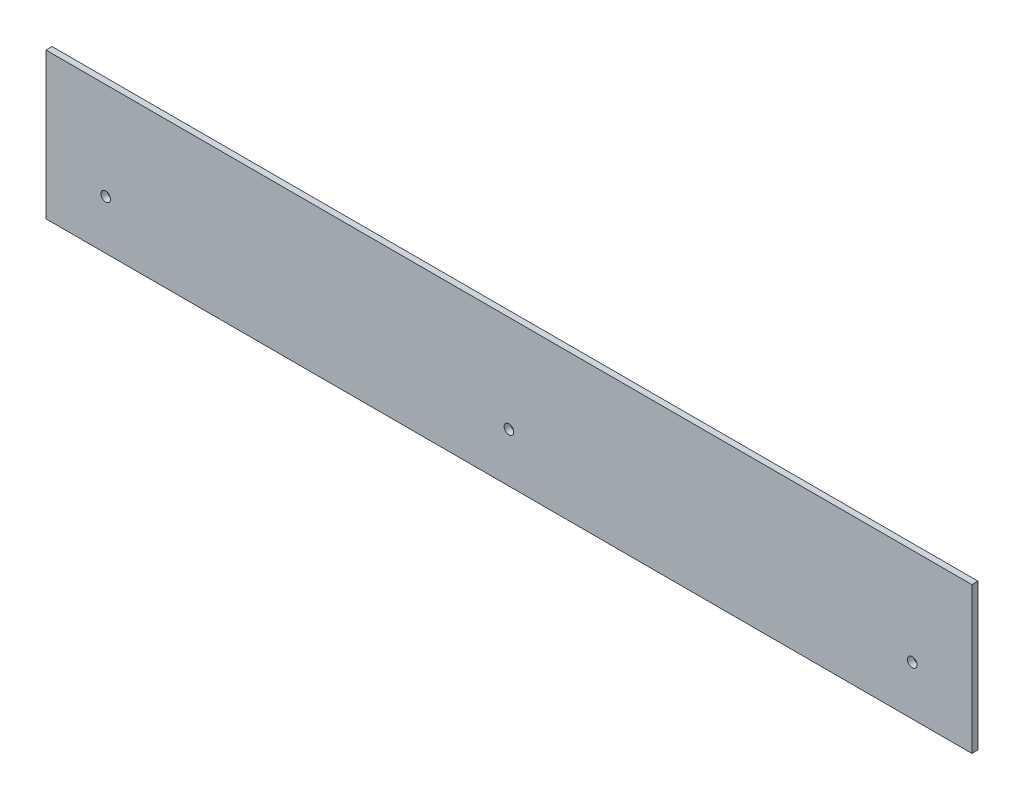
SolidWorks part; units mm, degrees
ref_plane "Front" through (0, 0, 0) normal (0, 0, 1) x (1, 0, 0)
ref_plane "Top" through (0, 0, 0) normal (0, 1, 0) x (1, 0, 0)
ref_plane "Right" through (0, 0, 0) normal (1, 0, 0) x (0, 0, -1)
sketch "Sketch1" plane through (0, 0, 0) normal (0, 0, 1) x (1, 0, 0)
  line L1 (-241.3, 38.1) -> (241.3, 38.1)
  line L2 (-241.3, 38.1) -> (-241.3, -38.1)
  line L3 (-241.3, -38.1) -> (241.3, -38.1)
  line L4 (241.3, 38.1) -> (241.3, -38.1)
  line L5 (-241.3, 38.1) -> (241.3, -38.1) construction
  line L6 (-241.3, -38.1) -> (241.3, 38.1) construction
  point P0 (0, 0)
  dimension "D1" = 482.6
  dimension "D2" = 76.2
extrude "Boss-Extrude1" add sketch "Sketch1" along normal blind 3.175 contours L1 L4 L3 L2
sketch "Sketch2" plane through (0, 0, 3.175) normal (0, 0, 1) x (1, 0, 0)
  line L0 (0, -1.7463) -> (0, 1.7463) construction
  line L4 (-241.3, 38.1) -> (-241.3, -38.1)
  line L5 (-241.3, -38.1) -> (241.3, -38.1)
  line L6 (241.3, -38.1) -> (241.3, 38.1)
  line L7 (241.3, 38.1) -> (-241.3, 38.1)
  line L8 (-241.3, 38.1) -> (-241.3, -38.1)
  line L9 (-241.3, -38.1) -> (241.3, -38.1)
  line L10 (241.3, -38.1) -> (241.3, 38.1)
  line L11 (241.3, 38.1) -> (-241.3, 38.1)
  circle A0 centre (-210.185, -12.446) radius 2.5
  circle A1 centre (210.185, -12.446) radius 2.5
  circle A2 centre (0, -12.446) radius 2.5
  point P12 (0, 0)
  dimension "D2" = 5
  dimension "D5" = 25.654
  dimension "D3" = 25.654
  dimension "D4" = 31.115
  dimension "D1" = 0
extrude "Cut-Extrude1" cut sketch "Sketch2" against normal through all contours A0 | A1 | A2
